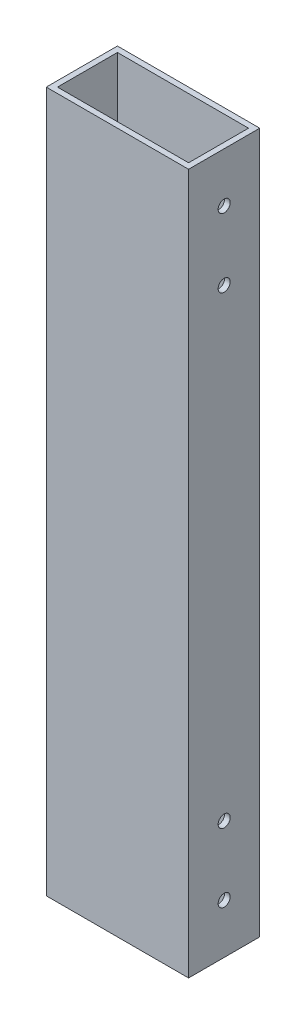
SolidWorks part; units mm, degrees
ref_plane "前基準面" through (0, 0, 0) normal (0, 0, 1) x (1, 0, 0)
ref_plane "上基準面" through (0, 0, 0) normal (0, 1, 0) x (1, 0, 0)
ref_plane "右基準面" through (0, 0, 0) normal (1, 0, 0) x (0, 0, -1)
sketch "草圖5" plane through (0, 0, 0) normal (0, 1, 0) x (1, 0, 0)
  line L0 (-23.4, -10.7) -> (-23.4, 10.7)
  line L1 (-25.4, -12.7) -> (25.4, -12.7)
  line L2 (-25.4, -12.7) -> (-25.4, 12.7)
  line L3 (-25.4, 12.7) -> (25.4, 12.7)
  line L4 (25.4, -12.7) -> (25.4, 12.7)
  line L5 (-25.4, -12.7) -> (25.4, 12.7) construction
  line L6 (-25.4, 12.7) -> (25.4, -12.7) construction
  line L7 (-23.4, 10.7) -> (23.4, 10.7)
  line L8 (23.4, -10.7) -> (23.4, 10.7)
  line L9 (-23.4, -10.7) -> (23.4, -10.7)
  point P0 (0, 0)
  dimension "D1" = 50.8
  dimension "D2" = 25.4
  dimension "D3" = 2
extrude "填料-伸長3" add sketch "草圖5" along normal blind 250 contours L1 L4 L3 L2
extrude "除料-伸長3" cut sketch "草圖5<7>" along normal through all contours L9 L8 L7 L0
sketch "草圖5<7>" plane through (0, 0, 0) normal (0, 1, 0) x (1, 0, 0) same geometry as "草圖5"
sketch "草圖6" plane through (-25.4, 0, 0) normal (-1, 0, 0) x (0, 0, 1)
  circle A0 centre (0, 232.3) radius 2.15
  circle A1 centre (0, 207.8) radius 2.15
  circle A2 centre (0, 42.2) radius 2.15
  circle A3 centre (0, 17.7) radius 2.15
extrude "除料-伸長4" cut sketch "草圖6" against normal blind 50.8
